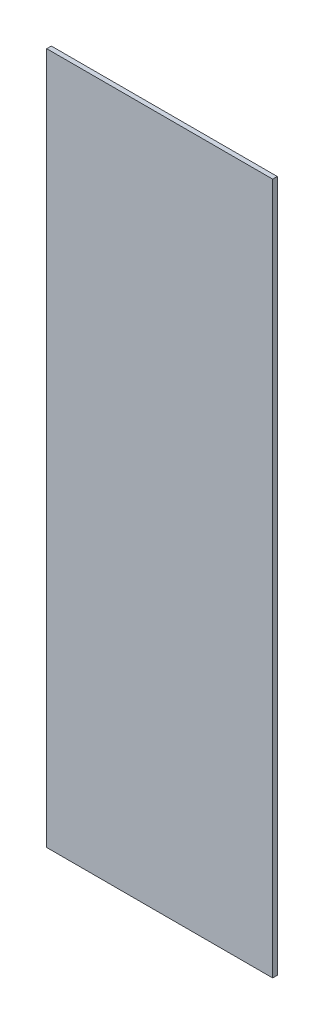
SolidWorks part; units mm, degrees
ref_plane "Front Plane" through (0, 0, 0) normal (0, 0, 1) x (1, 0, 0)
ref_plane "Top Plane" through (0, 0, 0) normal (0, 1, 0) x (1, 0, 0)
ref_plane "Right Plane" through (0, 0, 0) normal (1, 0, 0) x (0, 0, -1)
sketch "Sketch1" plane through (0, 0, 0) normal (0, 0, 1) x (1, 0, 0)
  line L1 (49, -150) -> (-49, -150)
  line L2 (49, -150) -> (49, 150)
  line L3 (49, 150) -> (-49, 150)
  line L4 (-49, -150) -> (-49, 150)
  line L5 (49, -150) -> (-49, 150) construction
  line L6 (49, 150) -> (-49, -150) construction
  point P0 (0, 0)
  dimension "D1" = 98
  dimension "D2" = 300
extrude "Boss-Extrude1" add sketch "Sketch1" along normal blind 2
sketch "Sketch2" plane through (0, 0, 2) normal (0, 0, 1) x (1, 0, 0)
  line L0 (-49, 150) -> (-49, -150) construction
  line L1 (49, 150) -> (-49, 150) construction
  line L2 (-49, -150) -> (49, -150) construction
  line L4 (0, -1.1) -> (0, 1.1) construction
  circle A0 centre (-39, 122) radius 1.5
  circle A1 centre (-39, 77) radius 1.5
  circle A2 centre (39, 122) radius 1.5
  circle A3 centre (39, 77) radius 1.5
  circle A4 centre (-39, 24) radius 1.5
  circle A5 centre (-39, -21) radius 1.5
  circle A6 centre (39, 24) radius 1.5
  circle A7 centre (39, -21) radius 1.5
  circle A8 centre (-39, -74) radius 1.5
  circle A9 centre (-39, -119) radius 1.5
  circle A10 centre (39, -74) radius 1.5
  circle A11 centre (39, -119) radius 1.5
  circle A13 centre (16.5, -147) radius 1.5
  circle A14 centre (-16.5, -147) radius 1.5
  circle A15 centre (-16.5, -49) radius 1.5
  circle A16 centre (16.5, -49) radius 1.5
  circle A17 centre (-16.5, 49) radius 1.5
  circle A18 centre (16.5, 49) radius 1.5
  circle A19 centre (-16.5, 147) radius 1.5
  circle A20 centre (16.5, 147) radius 1.5
  dimension "D1" = 3
  dimension "D3" = 28
  dimension "D4" = 3
  dimension "D6" = 10
  dimension "D10" = 3
  dimension "D11" = 33
  dimension "D13" = 3
  dimension "D2" = 10
  dimension "D5" = 45
  dimension "D9" = 31
  dimension "D7" = 2
  dimension "D8" = 3
  dimension "D12" = 4
